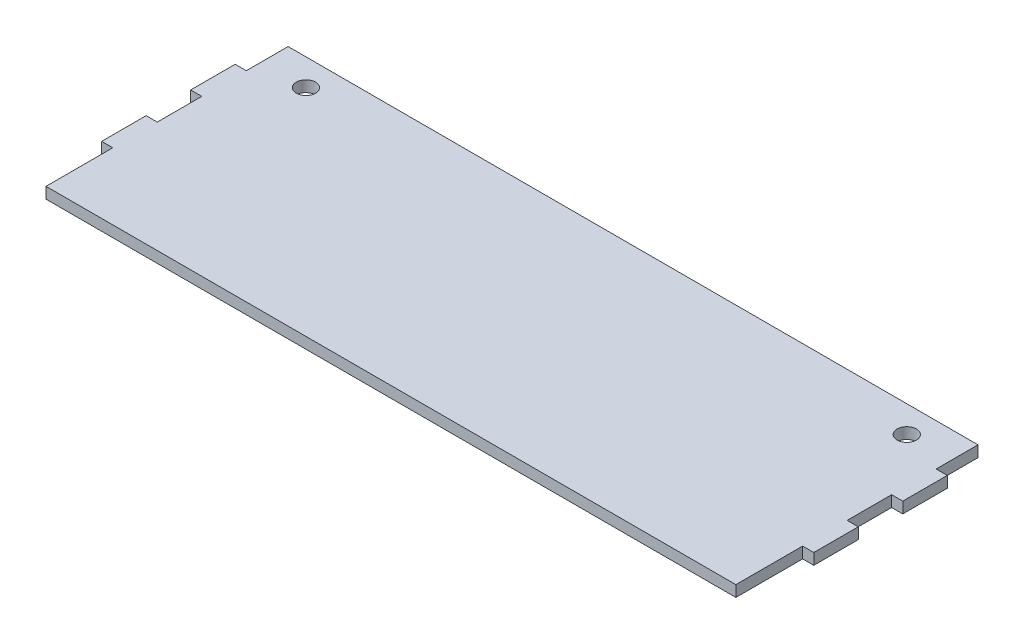
SolidWorks part; units mm, degrees
material "Acrylic (Medium-high impact)"
ref_plane "Front Plane" through (0, 0, 0) normal (0, 0, 1) x (1, 0, 0)
ref_plane "Top Plane" through (0, 0, 0) normal (0, 1, 0) x (1, 0, 0)
ref_plane "Right Plane" through (0, 0, 0) normal (1, 0, 0) x (0, 0, -1)
sketch "Sketch1" plane through (0, 0, 0) normal (0, 1, 0) x (1, 0, 0)
  line L0 (101.6, 69.088) -> (101.6, 0) construction
  line L37 (0, 0) -> (203.2, 0)
  line L38 (0, 0) -> (0, 69.088)
  line L39 (0, 69.088) -> (203.2, 69.088)
  line L40 (203.2, 0) -> (203.2, 69.088)
  line L41 (200.025, 57.15) -> (200.025, 69.088)
  line L42 (0, 0) -> (3.175, 0)
  line L43 (0, 0) -> (0, 19.05)
  line L44 (0, 19.05) -> (3.175, 19.05)
  line L45 (3.175, 0) -> (3.175, 19.05)
  line L46 (0, 31.75) -> (3.175, 31.75)
  line L47 (0, 31.75) -> (0, 44.45)
  line L48 (0, 44.45) -> (3.175, 44.45)
  line L49 (3.175, 31.75) -> (3.175, 44.45)
  line L50 (0, 57.15) -> (3.175, 57.15)
  line L51 (0, 57.15) -> (0, 69.088)
  line L52 (0, 69.088) -> (3.175, 69.088)
  line L53 (3.175, 57.15) -> (3.175, 69.088)
  line L54 (203.2, 69.088) -> (200.025, 69.088)
  line L55 (203.2, 57.15) -> (203.2, 69.088)
  line L56 (203.2, 57.15) -> (200.025, 57.15)
  line L57 (200.025, 31.75) -> (200.025, 44.45)
  line L58 (203.2, 44.45) -> (200.025, 44.45)
  line L59 (203.2, 31.75) -> (203.2, 44.45)
  line L60 (203.2, 31.75) -> (200.025, 31.75)
  line L61 (200.025, 0) -> (200.025, 19.05)
  line L62 (203.2, 19.05) -> (200.025, 19.05)
  line L63 (203.2, 0) -> (203.2, 19.05)
  line L64 (203.2, 0) -> (200.025, 0)
  line L65 (203.2, 0) -> (203.2, 69.088)
  dimension "D1" = 69.088
  dimension "D2" = 203.2
  dimension "D3" = 12.7
  dimension "D4" = 19.05
  dimension "D5" = 12.7
  dimension "D6" = 3.175
  dimension "D7" = 12.7
extrude "Boss-Extrude1" add sketch "Sketch1" along normal blind 3.175 contours L0 L39 L53 L50 L38 L48 L49 L46 L44 L45 L37 | L39 L0 L37 L61 L62 L40 L60 L57 L58 L56 L41 region at (151.4079, 0, -34.5857) region at (51.7921, 0, -34.5857)
hole_wizard "M5 Clearance Hole1" positions "Sketch5" profile "Sketch6" hole size "M5" standard "ANSI Metric" end condition through all
sketch "Sketch5" plane through (0, 3.175, 0) normal (0, 1, 0) x (1, 0, 0)
  line L0 (200.025, 57.15) -> (200.025, 69.088) construction
  line L2 (3.175, 57.15) -> (3.175, 69.088) construction
  line L3 (3.175, 69.088) -> (200.025, 69.088) construction
  point P0 (15.875, 61.468)
  point P2 (187.325, 61.468)
  dimension "D1" = 12.7
  dimension "D2" = 12.7
  dimension "D3" = 7.62
  dimension "D4" = 7.62
sketch "Sketch6" plane through (15.875, 3.175, -61.468) normal (1, 0, 0) x (0, 0, 1)
  line L0 (0, 0) -> (0, 3.175)
  line L1 (0, 3.175) -> (2.75, 3.175)
  line L2 (2.75, 3.175) -> (2.75, 0)
  line L5 (2.75, 0) -> (0, 0)
  line L11 (0, -6.35) -> (0, 107.95) construction
  dimension "Thru Hole Dia." = 5.5
  dimension "Thru Hole Depth" = 3.175
